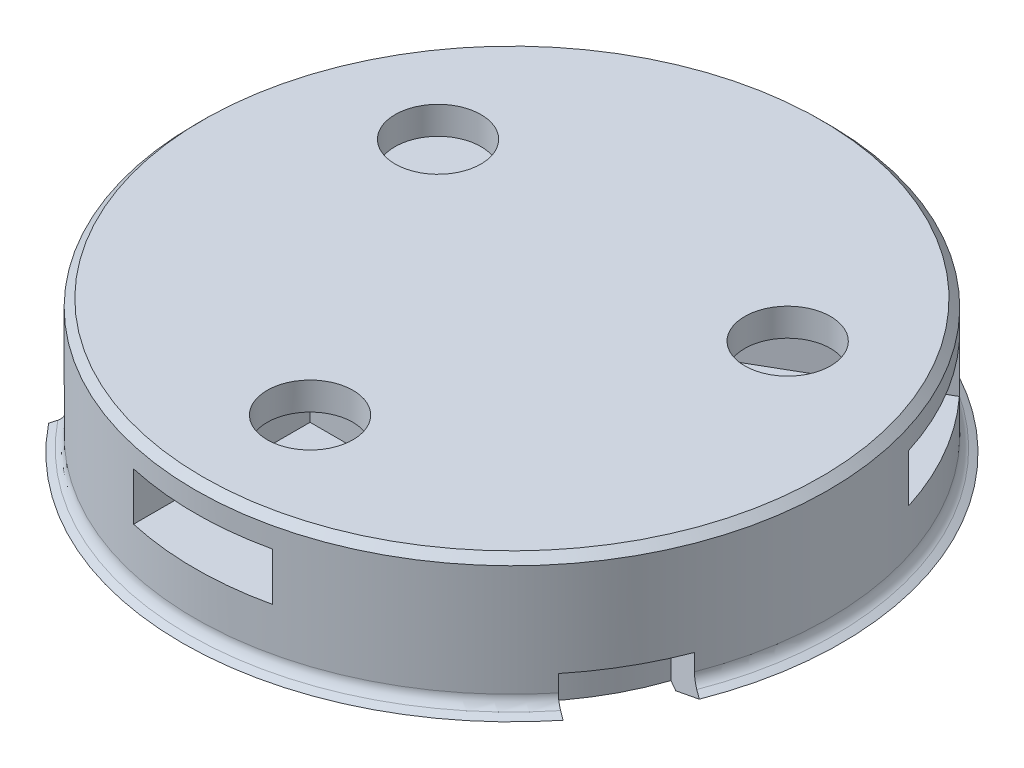
SolidWorks part; units mm, degrees
ref_plane "Front Plane" through (0, 0, 0) normal (0, 0, 1) x (1, 0, 0)
ref_plane "Top Plane" through (0, 0, 0) normal (0, 1, 0) x (1, 0, 0)
ref_plane "Right Plane" through (0, 0, 0) normal (1, 0, 0) x (0, 0, -1)
sketch "Sketch1" plane through (0, 0, 0) normal (0, 1, 0) x (1, 0, 0)
  circle A0 centre (0, 0) radius 10.05
  dimension "D1" = 20.1
extrude "Boss-Extrude1" add sketch "Sketch1" along normal blind 1.746
sketch "Sketch2" plane through (0, 1.746, 0) normal (0, 1, 0) x (1, 0, 0)
  circle A0 centre (0, 0) radius 12.55
  dimension "D1" = 25.1
extrude "Boss-Extrude2" add sketch "Sketch2" along normal blind 4
sketch "Sketch3" plane through (0, 0, 0) normal (0, -1, 0) x (1, 0, 0)
  circle A0 centre (0, 0) radius 3.25
  dimension "D1" = 6.5
extrude "Cut-Extrude1" cut sketch "Sketch3" against normal through all
sketch "Sketch4" plane through (0, 0, 0) normal (0, -1, 0) x (1, 0, 0)
  line L0 (0, 0) -> (0, 12.55) construction
  line L1 (0, 0) -> (0, 6.5) construction
  line L2 (0, 0) -> (5.6292, -3.25) construction
  circle A0 centre (0, 0) radius 12.55 construction
  circle A1 centre (0, 6.5) radius 2.525
  circle A2 centre (5.6292, -3.25) radius 2.525
  circle A3 centre (-5.6292, -3.25) radius 2.525
  dimension "D1" = 5.05
  dimension "D2" = 6.5
  dimension "D4" = 120
  dimension "D3" = 3
extrude "Cut-Extrude2" cut sketch "Sketch4" against normal blind 2.5
sketch "Sketch5" plane through (0, 2.5, 0) normal (0, -1, 0) x (1, 0, 0)
  circle A0 centre (0, 6.5) radius 1.75
  circle A1 centre (-5.6292, -3.25) radius 1.75
  circle A2 centre (5.6292, -3.25) radius 1.75
  dimension "D1" = 3.5
extrude "Cut-Extrude3" cut sketch "Sketch5" against normal blind 0.3
chamfer "Chamfer1" distance 0.3 angle 45 3 edges at (5.6292, 0, -5.775) (-5.6292, 0, -5.775) (0, 0, 3.975)
sketch "Sketch6" plane through (0, 0, 0) normal (0, -1, 0) x (1, 0, 0)
  line L0 (0, 0) -> (6.7117, 3.875) construction
  line L1 (0, 6.5) -> (5.6292, -3.25) construction
  line L2 (0, 0) -> (6.7117, 3.875) construction
  line L3 (0, 0) -> (0, -7.75) construction
  circle A0 centre (0, 0) radius 7.75 construction
  circle A1 centre (6.7117, 3.875) radius 1.1
  circle A2 centre (0, -7.75) radius 1.1
  circle A3 centre (-6.7117, 3.875) radius 1.1
  dimension "D1" = 15.5
  dimension "D2" = 2.2
  dimension "D3" = 3
  dimension "D4" = 120
extrude "Cut-Extrude4" cut sketch "Sketch6" against normal blind 2.5
ref_plane "Plane1" through (0, 1, 0) normal (0, -1, 0) x (-1, 0, 0)
ref_axis "Axis1" through (0, 5.746, 0) along (0, -1, 0)
sketch "Sketch10" plane through (0, 0, 0) normal (0, 0, 1) x (1, 0, 0)
  line L0 (10.05, 1.746) -> (13.5742, 1.746) construction
  line L2 (10.05, 0) -> (10.05, 1.746)
  line L3 (12.55, 1.746) -> (12.55, 5.746) construction
  line L4 (10.05, 1.746) -> (12.55, 1.746)
  line L11 (-10.05, 0) -> (10.05, 0) construction
  line L12 (10.05, 0) -> (10.55, 0) construction
  line L13 (10.55, 0) -> (13.5742, 1.746) construction
  line L14 (10.05, 0) -> (10.55, 0)
  line L15 (12.55, 1.746) -> (13.0621, 1.4504)
  line L17 (13.0621, 1.4504) -> (10.55, 0)
  dimension "D1" = 150
  dimension "D2" = 30
  dimension "D3" = 0.5
  dimension "D4" = 0.5121
revolve "Revolve1" add sketch "Sketch10" angle 360 about axis through (0, 5.746, 0) along (0, -1, 0)
sketch "Sketch7" plane through (0, 1, 0) normal (0, -1, 0) x (-1, 0, 0)
  line L0 (-1.975, 8.8903) -> (-1.975, 18.8903)
  line L1 (0, 10.0305) -> (-1.975, 8.8903) construction
  line L2 (-1.975, 8.8903) -> (-1.975, 6.6097)
  line L3 (-1.975, 6.6097) -> (0, 5.4695)
  line L4 (0, 5.4695) -> (1.975, 6.6097)
  line L5 (1.975, 6.6097) -> (1.975, 8.8903)
  line L6 (1.975, 8.8903) -> (0, 10.0305) construction
  line L7 (-1.975, 18.8903) -> (1.975, 18.8903)
  line L8 (1.975, 18.8903) -> (1.975, 8.8903)
  circle A0 centre (0, 7.75) radius 1.975 construction
  dimension "D1" = 3.95
  dimension "D2" = 10
extrude "Cut-Extrude5" cut sketch "Sketch7" against normal blind 1.7
sketch "Sketch11" plane through (0, 0, 0) normal (0, -1, 0) x (1, 0, 0)
  line L0 (1.975, -12.3936) -> (1.975, -6.6097) construction
  line L1 (-1.975, -19.854) -> (-1.975, -9.854)
  line L2 (1.975, -19.854) -> (1.975, -9.854)
  line L3 (-1.975, -6.6097) -> (-1.975, -12.3936) construction
  arc A0 (-1.975, -19.854) -> (1.975, -19.854) centre (0, 0) ccw
  arc A3 (-1.975, -9.854) -> (1.975, -9.854) centre (0, 0) ccw
  dimension "D1" = 10.05
  dimension "D2" = 10
extrude "Cut-Extrude6" cut sketch "Sketch11" against normal up to surface (2.7 mm away) up to face at (0, 2.7, -8.7265)
pattern_circular "CirPattern1" count 3 over 360 about axis through (0, 5.746, 0) along (0, -1, 0) of "Cut-Extrude5", "Cut-Extrude6"
fillet "Fillet1" radius 0.5 3 edges at (-10.8686, 1.746, -6.275) (0, 1.746, 12.55) (10.8686, 1.746, -6.275)
sketch "Sketch12" plane through (0, 5.746, 0) normal (0, 1, 0) x (1, 0, 0)
  circle A0 centre (0, 0) radius 12.55
  circle A1 centre (0, 0) radius 12.55 construction
extrude "Boss-Extrude3" add sketch "Sketch12" along normal blind 1
sketch "Sketch13" plane through (0, 6.746, 0) normal (0, 1, 0) x (1, 0, 0)
  circle A0 centre (0, 0) radius 8 construction
  circle A1 centre (0, -8) radius 1.7
  circle A2 centre (-6.9282, 4) radius 1.7
  circle A3 centre (6.9282, 4) radius 1.7
  point P14 (0, 0)
  dimension "D1" = 16
  dimension "D2" = 3.4
  dimension "D3" = 3
extrude "Cut-Extrude7" cut sketch "Sketch13" against normal blind 3
sketch "Sketch14" [suppressed] plane through (0, 3.746, 0) normal (0, 1, 0) x (1, 0, 0)
  line L0 (-2.7, -9.5588) -> (-2.7, -14.5588)
  line L1 (0, -11.1177) -> (2.7, -9.5588) construction
  line L2 (2.7, -9.5588) -> (2.7, -6.4412)
  line L3 (2.7, -6.4412) -> (0, -4.8823)
  line L4 (0, -4.8823) -> (-2.7, -6.4412)
  line L5 (-2.7, -6.4412) -> (-2.7, -9.5588)
  line L6 (-2.7, -9.5588) -> (0, -11.1177) construction
  line L7 (-2.7, -14.5588) -> (2.7, -14.5588)
  line L8 (2.7, -14.5588) -> (2.7, -9.5588)
  circle A0 centre (0, -8) radius 2.7 construction
  dimension "D1" = 5.4
  dimension "D2" = 5
extrude "Cut-Extrude8" [suppressed] cut sketch "Sketch14" along normal blind 2.7
pattern_circular "CirPattern3" [suppressed] count 3 over 360 about axis through (0, 5.746, 0) along (0, -1, 0) of bodies 113
fillet "4 Holes Fillet" [suppressed] radius 0.5
fillet "3 Holes Fillet" [suppressed] radius 0.5
sketch "Sketch15" plane through (0, 3.746, 0) normal (0, 1, 0) x (1, 0, 0)
  line L0 (-2.75, -10.75) -> (-2.75, -15.75)
  line L1 (-2.75, -10.75) -> (2.75, -10.75) construction
  line L2 (-2.75, -10.75) -> (-2.75, -5.25)
  line L3 (-2.75, -5.25) -> (2.75, -5.25)
  line L4 (2.75, -10.75) -> (2.75, -5.25)
  line L5 (-2.75, -10.75) -> (2.75, -5.25) construction
  line L6 (-2.75, -5.25) -> (2.75, -10.75) construction
  line L7 (-2.75, -15.75) -> (2.75, -15.75)
  line L8 (2.75, -15.75) -> (2.75, -10.75)
  line L9 (-15.0149, 5.4934) -> (-10.6848, 2.9934)
  line L10 (-10.6848, 2.9934) -> (-5.9216, 0.2434)
  line L11 (-3.1716, 5.0066) -> (-5.9216, 0.2434)
  line L12 (-7.9348, 7.7566) -> (-3.1716, 5.0066)
  line L13 (-7.9348, 7.7566) -> (-12.2649, 10.2566)
  line L14 (-12.2649, 10.2566) -> (-15.0149, 5.4934)
  line L15 (12.2649, 10.2566) -> (7.9348, 7.7566)
  line L16 (7.9348, 7.7566) -> (3.1716, 5.0066)
  line L17 (5.9216, 0.2434) -> (3.1716, 5.0066)
  line L18 (10.6848, 2.9934) -> (5.9216, 0.2434)
  line L19 (10.6848, 2.9934) -> (15.0149, 5.4934)
  line L20 (15.0149, 5.4934) -> (12.2649, 10.2566)
  point P0 (0, -8)
  point P22 (0, 0)
  dimension "D1" = 5
  dimension "D2" = 5.5
  dimension "D3" = 3
extrude "Cut-Extrude9" cut sketch "Sketch15" along normal blind 1.9
chamfer "Chamfer2" distance 0.3 angle 45 1 edges at (0, 6.746, 12.55)
fillet "Fillet2" [suppressed] radius 0.5
fillet "Fillet3" [suppressed] radius 0.5
